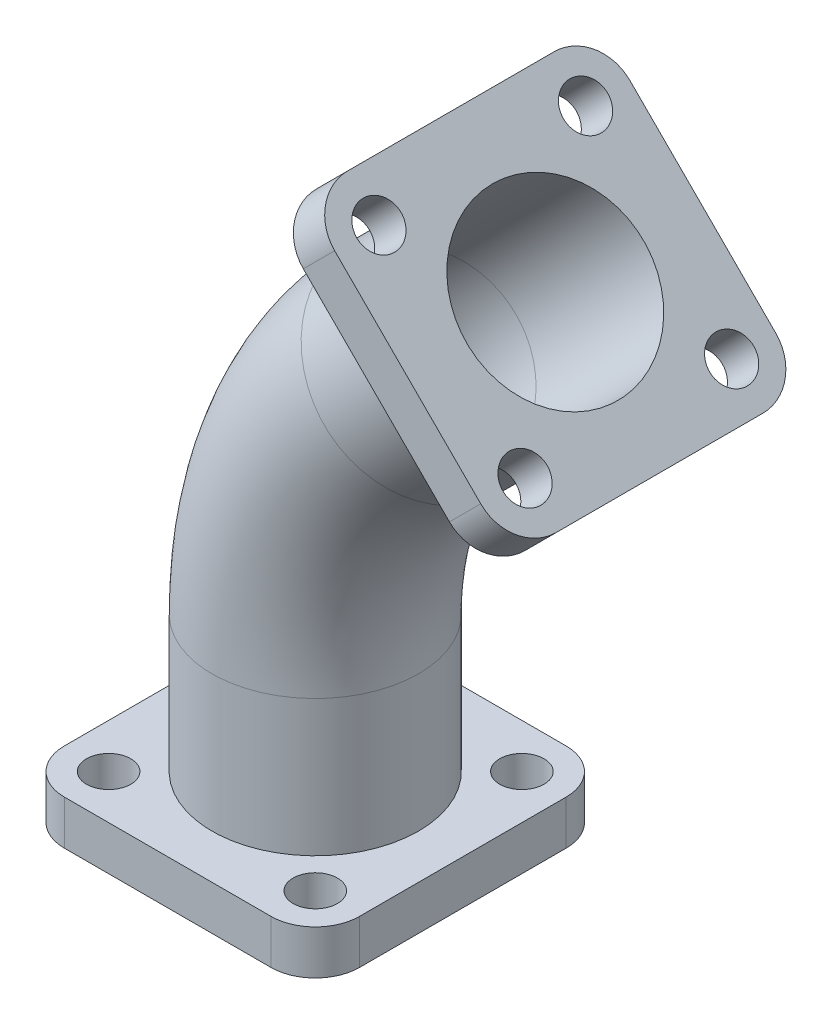
SolidWorks part; units mm, degrees
ref_plane "Alzado" through (0, 0, 0) normal (0, 0, 1) x (1, 0, 0)
ref_plane "Planta" through (0, 0, 0) normal (0, 1, 0) x (1, 0, 0)
ref_plane "Vista lateral" through (0, 0, 0) normal (1, 0, 0) x (0, 0, -1)
sketch "Croquis1" plane through (0, 0, 0) normal (0, 0, 1) x (1, 0, 0)
  line L0 (0, 37.4324) -> (0, -59.2473) construction
  line L1 (-50, 0) -> (50, 0) construction
  line L2 (-50, 0) -> (50, 0)
  line L3 (-50, 0) -> (-50, 15)
  line L4 (50, 0) -> (50, 15)
  line L5 (-50, 15) -> (50, 15)
  point P5 (0, 0)
  dimension "D1" = 100
  dimension "D2" = 15
extrude "Saliente-Extruir1" add sketch "Croquis1" along normal mid plane 100
sketch "Croquis17" plane through (0, 15, 0) normal (0, 1, 0) x (1, 0, 0)
  line L0 (0, 50) -> (0, -50) construction
  line L1 (50, 50) -> (-50, 50) construction
  line L2 (50, -50) -> (-50, -50) construction
  line L3 (-50, 0) -> (50, 0) construction
  line L4 (-50, -50) -> (-50, 50) construction
  line L5 (50, -50) -> (50, 50) construction
  circle A0 centre (0, 0) radius 30
extrude "Cortar-Extruir1" cut sketch "Croquis17" against normal up to surface (15 mm away) from surface up to face at (0, 0, 0) starting at face at (0, 15, 0)
sketch "Croquis2" plane through (0, 0, 0) normal (0, 0, 1) x (1, 0, 0)
  line L0 (0, 0) -> (0, 61.1522)
  line L1 (38.0761, 153.0761) -> (70.7107, 185.7107)
  arc A0 (38.0761, 153.0761) -> (0, 61.1522) centre (130, 61.1522) ccw
  dimension "D1" = 135
sweep "Barrer1" add path "Croquis2" circular profile diameter 70 parameters "D3"=70
sweep "Cortar-Barrer2" cut path "Croquis2<5>" circular profile diameter 60 parameters "D3"=60
sketch "Croquis2<5>" plane through (0, 0, 0) normal (0, 0, 1) x (1, 0, 0) same geometry as "Croquis2"
fillet "Redondeo1" radius 15 4 edges at (-50, 7.5, -50) (50, 7.5, -50) (-50, 7.5, 50) (50, 7.5, 50)
hole_wizard "Taladro1" positions "Croquis3D1" profile "Croquis25" legacy
sketch3d "Croquis3D1"
  line L0 (-35, 0, -35) -> (-35, 15, -35) construction
  line L1 (-35, 15, 35) -> (-35, 0, 35) construction
  line L2 (35, 15, -35) -> (35, 0, -35) construction
  line L3 (35, 0, 35) -> (35, 15, 35) construction
  point P0 (-35, 15, -35)
  point P4 (-35, 15, 35)
  point P8 (35, 15, -35)
  point P12 (35, 15, 35)
sketch "Croquis25" plane through (-35, 15, -35) normal (1, 0, 0) x (0, 0, 1)
  line L0 (0, 0) -> (0, 15)
  line L1 (0, 15) -> (7.5, 15)
  line L2 (7.5, 15) -> (7.5, 0)
  line L3 (7.5, 0) -> (0, 0)
  line L4 (0, 110) -> (0, -10) construction
  dimension "Diámetro" = 15
  dimension "Profundidad" = 15
sketch "Croquis26" plane through (128.2107, 128.2107, 0) normal (0.7071, 0.7071, 0) x (0, 0, -1)
  line L0 (0, 43.2412) -> (0, 120.7565) construction
  line L1 (0, 81.3173) -> (0, 43.2412) construction
  line L2 (0, 0) -> (0, 43.2412) construction
  line L3 (-30, 81.3173) -> (30, 81.3173) construction
  line L5 (-50, 31.3173) -> (50, 31.3173)
  line L6 (-50, 131.3173) -> (50, 131.3173)
  line L7 (-50, 31.3173) -> (-50, 131.3173)
  line L8 (50, 31.3173) -> (50, 131.3173)
extrude "Saliente-Extruir3" add sketch "Croquis26" along normal blind 15
fillet "Redondeo2" radius 15 4 edges at (40.6586, 226.3693, 50) (111.3693, 155.6586, 50) (40.6586, 226.3693, -50) (111.3693, 155.6586, -50)
sketch "Croquis29" plane through (138.8173, 138.8173, 0) normal (0.7071, 0.7071, 0) x (0, 0, -1)
  line L0 (0, 81.3173) -> (0, 43.2412) construction
  circle A0 centre (0, 81.3173) radius 30
extrude "Cortar-Extruir2" cut sketch "Croquis29" against normal blind 15
hole_wizard "Taladro2" positions "Croquis3D3" profile "Croquis30" legacy end condition up to next
sketch3d "Croquis3D3"
  line L0 (56.5685, 221.066, 35) -> (45.9619, 210.4594, 35) construction
  line L1 (106.066, 171.5685, 35) -> (95.4594, 160.9619, 35) construction
  line L2 (106.066, 171.5685, -35) -> (95.4594, 160.9619, -35) construction
  line L3 (56.5685, 221.066, -35) -> (45.9619, 210.4594, -35) construction
  point P0 (56.5685, 221.066, 35)
  point P4 (106.066, 171.5685, 35)
  point P8 (106.066, 171.5685, -35)
  point P12 (56.5685, 221.066, -35)
sketch "Croquis30" plane through (56.5685, 221.066, 35) normal (0, 0, 1) x (-0.7071, 0.7071, 0)
  line L0 (0, 0) -> (0, 15)
  line L1 (0, 15) -> (7.5, 15)
  line L2 (7.5, 15) -> (7.5, 0)
  line L3 (7.5, 0) -> (0, 0)
  line L4 (0, 110) -> (0, -10) construction
  dimension "Diámetro" = 15
  dimension "Profundidad" = 15
